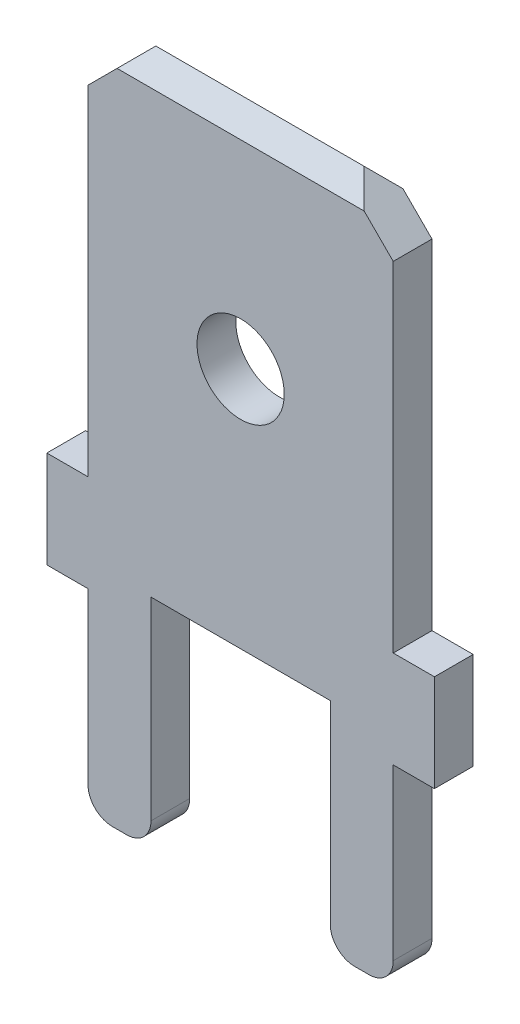
SolidWorks part; units mm, degrees
ref_plane "Plan de face" through (0, 0, 0) normal (0, 0, 1) x (1, 0, 0)
ref_plane "Plan de dessus" through (0, 0, 0) normal (0, 1, 0) x (1, 0, 0)
ref_plane "Plan de droite" through (0, 0, 0) normal (1, 0, 0) x (0, 0, -1)
sketch "Esquisse1" plane through (0, 0, 0) normal (0, 0, 1) x (1, 0, 0)
  line L0 (0, 0) -> (0, 10) construction
  line L1 (5, 0) -> (5, 10) construction
  line L2 (-0.65, 0) -> (0.65, 0)
  line L3 (0.65, 0) -> (0.65, 4.5)
  line L4 (0.65, 4.5) -> (4.35, 4.5)
  line L5 (4.35, 4.5) -> (4.35, 0)
  line L6 (4.35, 0) -> (5.65, 0)
  line L7 (5.65, 0) -> (5.65, 4)
  line L8 (-0.65, 0) -> (-0.65, 4)
  line L9 (-0.65, 4) -> (-1.5, 4)
  line L10 (-1.5, 4) -> (-1.5, 6)
  line L11 (-1.5, 6) -> (-0.65, 6)
  line L12 (6.5, 6) -> (6.5, 4)
  line L13 (6.5, 4) -> (5.65, 4)
  line L14 (-0.65, 6) -> (-0.65, 13)
  line L15 (0.35, 14) -> (4.65, 14)
  line L16 (5.65, 13) -> (5.65, 6)
  line L17 (5.65, 6) -> (6.5, 6)
  line L18 (4.65, 14) -> (5.65, 13)
  line L19 (-0.65, 13) -> (0.35, 14)
  line L20 (-0.65, 14) -> (5.65, 14) construction
  point P12 (-0.65, 14)
  point P19 (2.5, 4.5)
  point P20 (5.65, 14)
  point P22 (2.5, 14)
  dimension "D3" = 1.3
  dimension "D1" = 5
  dimension "D2" = 10
  dimension "D4" = 1.3
  dimension "D5" = 8
  dimension "D6" = 6.3
  dimension "D7" = 14
  dimension "D8" = 4
  dimension "D9" = 6
  dimension "D10" = 9.5
  dimension "D11" = 0.85
  dimension "D12" = 0.85
extrude "Extrusion1" add sketch "Esquisse1" along normal blind 0.8
chamfer "Chanfrein1" distance 0.4 angle 45 2 edges at (2.5, 14, 0.8) (2.5, 14, 0)
fillet "Congé1" radius 0.5 4 edges at (5.65, 0, 0.4) (-0.65, 0, 0.4) (4.35, 0, 0.4) (0.65, 0, 0.4)
sketch "Esquisse2" plane through (0, 0, 0) normal (0, -1, 0) x (1, 0, 0)
  line L0 (-0.15, 0.4) -> (5.15, 0.4) construction
  line L1 (-0.15, 0.8) -> (-0.15, 0) construction
  line L2 (5.15, 0) -> (5.15, 0.8) construction
  circle A0 centre (0, 0.4) radius 0.25
  circle A1 centre (5, 0.4) radius 0.25
  point P6 (2.5, 0.4)
  dimension "D1" = 5
  dimension "D3" = 0.5
  dimension "D4" = 0.5
  dimension "D2" = 2.5
sketch "Sketch1" plane through (0, 0, 0.8) normal (0, 0, 1) x (1, 0, 0)
  line L0 (2.5, 14) -> (2.5, 9.5) construction
  line L1 (4.65, 14) -> (0.35, 14) construction
  circle A0 centre (2.5, 9.5) radius 0.9
  dimension "D2" = 1.8
  dimension "D1" = 4.5
extrude "Cut-Extrude1" cut sketch "Sketch1" against normal through all
sketch "Sketch2" plane through (0, 0, 0) normal (0, -1, 0) x (1, 0, 0)
  line L0 (0, 0.4) -> (5, 0.4) construction
  line L1 (-0.15, 0.4) -> (0, 0.4) construction
  line L2 (-0.15, 0.8) -> (-0.15, 0) construction
  line L3 (2.5, 0) -> (2.5, 0.4) construction
  line L4 (0.65, 0) -> (4.35, 0) construction
  circle A0 centre (0, 0.4) radius 0.1427
  circle A1 centre (5, 0.4) radius 0.1573
  dimension "D1" = 5
